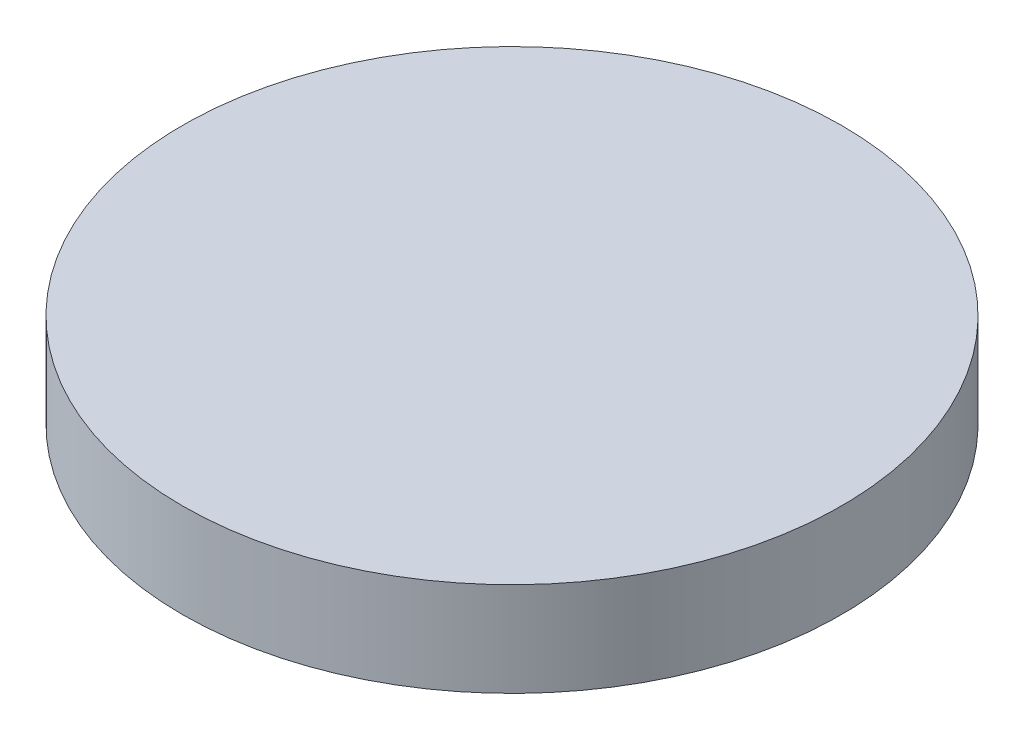
SolidWorks part; units mm, degrees
ref_plane "Front Plane" through (0, 0, 0) normal (0, 0, 1) x (1, 0, 0)
ref_plane "Top Plane" through (0, 0, 0) normal (0, 1, 0) x (1, 0, 0)
ref_plane "Right Plane" through (0, 0, 0) normal (1, 0, 0) x (0, 0, -1)
sketch "Sketch1" plane through (0, 0, 0) normal (0, 1, 0) x (1, 0, 0)
  circle A0 centre (0, 0) radius 10.5
  dimension "D1" = 21
extrude "Boss-Extrude1" add sketch "Sketch1" along normal blind 3
